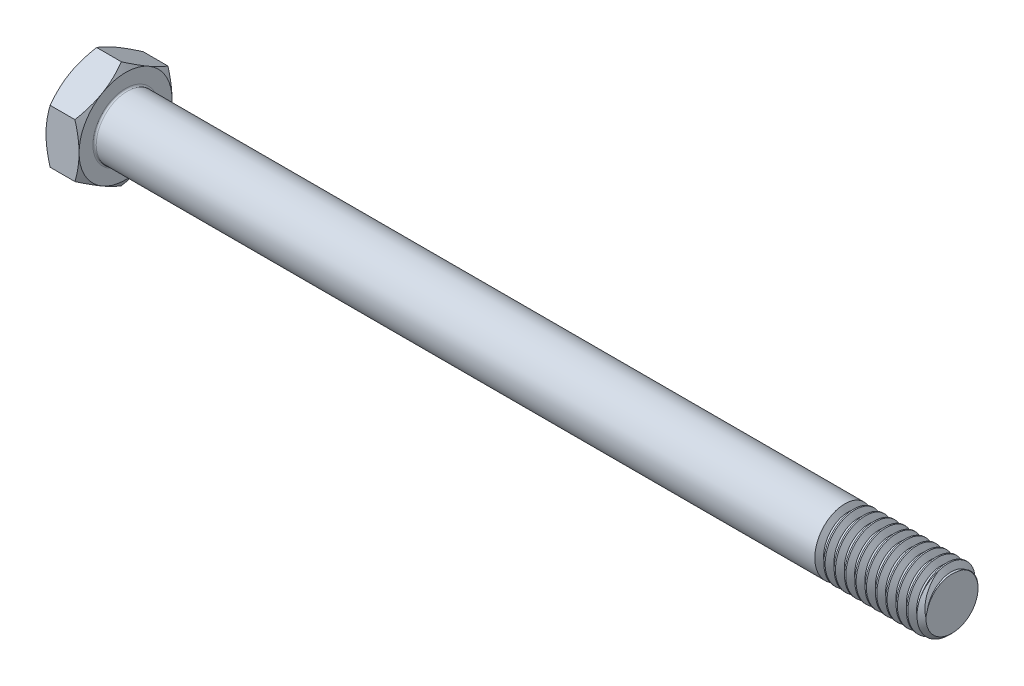
SolidWorks part; units mm, degrees
material "Plain Carbon Steel"
ref_plane "Front Plane" through (0, 0, 0) normal (0, 0, 1) x (1, 0, 0)
ref_plane "Top Plane" through (0, 0, 0) normal (0, 1, 0) x (1, 0, 0)
ref_plane "Right Plane" through (0, 0, 0) normal (1, 0, 0) x (0, 0, -1)
sketch "Sketch1" plane through (0, 0, 0) normal (0, 0, 1) x (1, 0, 0)
  line L0 (0, 0) -> (132.08, 0) construction
  line L1 (132.08, 0) -> (132.08, 4.0005)
  line L3 (131.318, 4.7625) -> (5.334, 4.7625)
  line L4 (5.08, 5.0165) -> (5.08, 7.1437)
  line L5 (5.08, 7.1437) -> (4.4419, 8.2489)
  line L6 (4.4419, 8.2489) -> (0.6381, 8.2489)
  line L7 (0.6381, 8.2489) -> (0, 7.1438)
  line L8 (0, 7.1438) -> (0, 0)
  line L9 (132.08, 4.0005) -> (131.318, 4.7625)
  line L10 (0, 8.2489) -> (-7.1438, 4.1244) construction
  line L11 (-7.1438, 4.1244) -> (-7.1438, -4.1244) construction
  line L12 (-7.1438, -4.1244) -> (0, -8.2489) construction
  line L13 (0, -8.2489) -> (7.1437, -4.1244) construction
  line L14 (7.1437, -4.1244) -> (7.1437, 4.1244) construction
  line L15 (7.1437, 4.1244) -> (0, 8.2489) construction
  line L16 (0, 0) -> (132.08, 0)
  arc A0 (5.334, 4.7625) -> (5.08, 5.0165) centre (5.334, 5.0165) cw
  circle A1 centre (0, 0) radius 7.1438 construction
  point P3 (0, 0)
  point P5 (132.08, 4.7625)
  point P8 (-1.7158, 11.3142)
  point P13 (0, 0)
  point P23 (0, 7.1438)
  dimension "D5" = 14.2875
  dimension "D7" = 0.254
  dimension "D1" = 9.525
  dimension "D2" = 127
  dimension "D3" = 30
  dimension "D6" = 5.08
revolve "Revolve1" add sketch "Sketch1" angle 360 about L16
sketch "Sketch2" plane through (0, 0, 0) normal (-1, 0, 0) x (0, 0, 1)
  line L1 (0, 8.2489) -> (-7.1438, 4.1244)
  line L2 (-7.1438, 4.1244) -> (-7.1437, -4.1244)
  line L3 (-7.1437, -4.1244) -> (0, -8.2489)
  line L4 (0, -8.2489) -> (7.1438, -4.1244)
  line L5 (7.1438, -4.1244) -> (7.1437, 4.1244)
  line L6 (7.1437, 4.1244) -> (0, 8.2489)
  circle A0 centre (0, 0) radius 7.1438 construction
  circle A1 centre (0, 0) radius 8.2489 construction
  point P1 (0, 8.2489)
extrude "Cut-Extrude1" cut sketch "Sketch2" against normal through all flip side to cut
thread "Thread1" pitch 1.5875 method cut profile "Thread Profile1" start angle 0, offset 2.54, length 18.415, pitch 1.5875, diameter 9.525
ref_plane "Plane1" through (134.62, 0, 4.7625) normal (0, -1, 0) x (0, 0, 1)
sketch "Thread Profile1" plane through (134.62, 0, 4.7625) normal (0, -1, 0) x (0, 0, 1)
  line L0 (0, 0) -> (0, 1.5875) construction
  line L11 (0, 0) -> (0, 1.3891)
  line L12 (0, 1.3891) -> (-0.8593, 0.893)
  line L13 (-0.8593, 0.893) -> (-0.8593, 0.4961)
  line L15 (-0.8593, 0.4961) -> (0, 0)
  line L17 (-0.8593, 0.6945) -> (0, 0.6945) construction
  point P2 (0, 0)
  dimension "Pitch" = 1.5875
  dimension "Profile_Angle" = 60
  dimension "Profile_Land" = 0.3969
  dimension "Profile_Height" = 0.8593
sketch "Sketch6" plane through (0, -0.0005, 0.0004) normal (0, 0.809, -0.5878) x (1, 0, 0)
  line L4 (115.708, 3.9012) -> (116.2041, 4.7604)
  line L5 (116.2041, 4.7604) -> (114.815, 4.7604)
  line L6 (114.815, 4.7604) -> (115.3111, 3.9012)
  line L7 (115.3111, 3.9012) -> (115.708, 3.9012)
  line L8 (115.708, 3.9012) -> (116.2041, 4.7604)
  line L9 (116.2041, 4.7604) -> (114.815, 4.7604)
  line L10 (114.815, 4.7604) -> (115.3111, 3.9012)
  line L11 (115.3111, 3.9012) -> (115.708, 3.9012)
  dimension "D1" = 0
extrude "Cut-Extrude2" cut sketch "Sketch6" against normal through all
